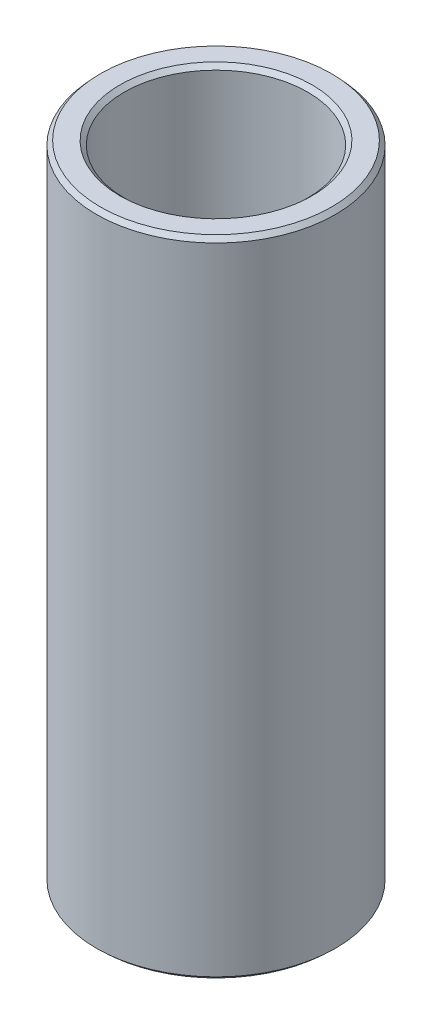
SolidWorks part; units mm, degrees
ref_plane "Front Plane" through (0, 0, 0) normal (0, 0, 1) x (1, 0, 0)
ref_plane "Top Plane" through (0, 0, 0) normal (0, 1, 0) x (1, 0, 0)
ref_plane "Right Plane" through (0, 0, 0) normal (1, 0, 0) x (0, 0, -1)
sketch "Sketch1" plane through (0, 0, 0) normal (0, 1, 0) x (1, 0, 0)
  circle A0 centre (0, 0) radius 27.5
  dimension "SLEEVE_OD" = 55
extrude "Boss-Extrude1" add sketch "Sketch1" along normal blind 148.0904
sketch "Sketch2" plane through (0, 0, 0) normal (0, 1, 0) x (1, 0, 0)
  circle A0 centre (0, 0) radius 21.0939
  dimension "BORE_D" = 42.1879
extrude "Cut-Extrude1" cut sketch "Sketch2" along normal through all
chamfer "Chamfer1" distance 1.0113 angle 42.64 4 edges at (0, 148.0904, 21.0939) (0, 0, 21.0939) (0, 0, 27.5) (0, 148.0904, 27.5) first distance on face at (0, 148.0904, 21.0939) first distance on face at (0, 0, 21.0939) first distance on face at (0, 148.0904, 27.5)
